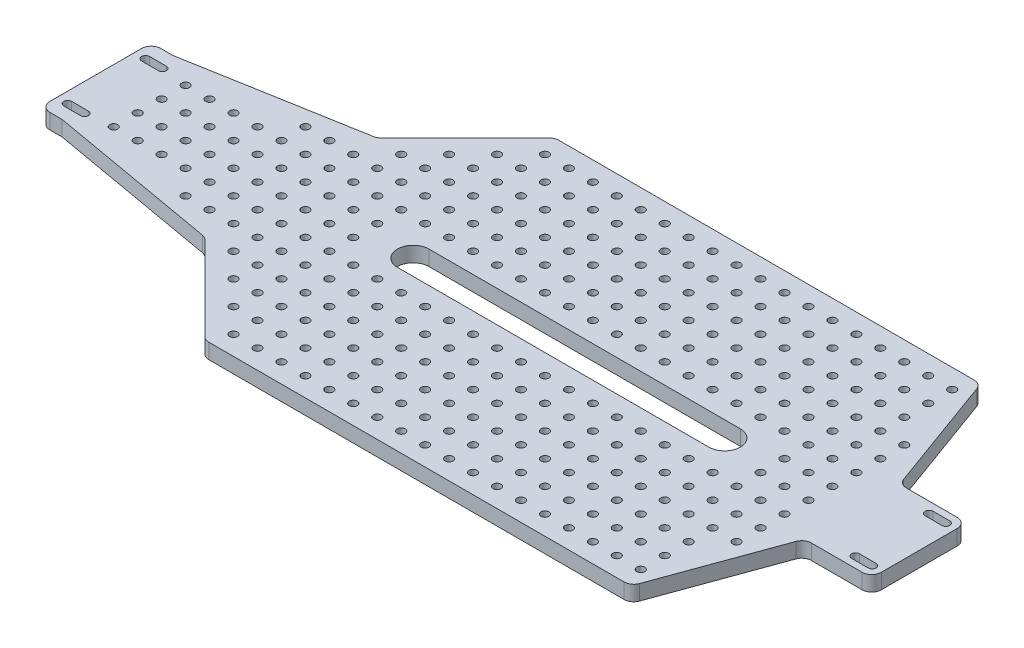
SolidWorks part; units mm, degrees
ref_plane "Front Plane" through (0, 0, 0) normal (0, 0, 1) x (1, 0, 0)
ref_plane "Top Plane" through (0, 0, 0) normal (0, 1, 0) x (1, 0, 0)
ref_plane "Right Plane" through (0, 0, 0) normal (1, 0, 0) x (0, 0, -1)
sketch "Sketch1" plane through (0, 0, 0) normal (0, 1, 0) x (1, 0, 0)
  line L0 (0, 32.5) -> (0, 0) construction
  line L17 (4.55, 39.385) -> (76.916, 52.1451)
  line L18 (0, 16.25) -> (325.2, 16.25) construction
  line L19 (-4.55, 39.385) -> (4.55, 39.385)
  line L20 (-4.55, 39.385) -> (-4.55, -6.885)
  line L21 (-4.55, -6.885) -> (4.55, -6.885)
  line L23 (-4.55, 39.385) -> (4.55, -6.885) construction
  line L24 (-4.55, -6.885) -> (4.55, 39.385) construction
  line L25 (311.2, -3.6) -> (339.2, -3.6)
  line L27 (311.2, 36.1) -> (339.2, 36.1)
  line L28 (339.2, -3.6) -> (339.2, 36.1)
  line L29 (311.2, -3.6) -> (339.2, 36.1) construction
  line L30 (311.2, 36.1) -> (339.2, -3.6) construction
  line L31 (202.9459, 16.25) -> (202.9459, 89.275) construction
  line L32 (291.8459, 89.275) -> (114.0459, 89.275)
  line L33 (311.2, 36.1) -> (291.8459, 89.275)
  line L34 (114.0459, 89.275) -> (76.916, 52.1451)
  line L35 (311.2, -3.6) -> (291.8459, -56.775)
  line L36 (291.8459, -56.775) -> (114.0459, -56.775)
  line L37 (114.0459, -56.775) -> (76.916, -19.6451)
  line L38 (4.55, -6.885) -> (76.916, -19.6451)
  line L39 (0, 32.5) -> (7, 32.5) construction
  line L40 (0, 34.15) -> (7, 34.15)
  line L41 (0, 30.85) -> (7, 30.85)
  line L42 (334.93, 31.625) -> (327.93, 31.625) construction
  line L43 (334.93, 29.975) -> (327.93, 29.975)
  line L44 (334.93, 33.275) -> (327.93, 33.275)
  line L45 (334.93, 0.875) -> (327.93, 0.875) construction
  line L46 (334.93, 2.525) -> (327.93, 2.525)
  line L47 (334.93, -0.775) -> (327.93, -0.775)
  line L48 (0, 0) -> (7, 0) construction
  line L49 (0, -1.65) -> (7, -1.65)
  line L50 (0, 1.65) -> (7, 1.65)
  circle A0 centre (0, 0) radius 1.65
  circle A1 centre (0, 32.5) radius 1.65 construction
  circle A4 centre (334.93, 31.625) radius 1.65 construction
  arc A5 (0, 34.15) -> (0, 30.85) centre (0, 32.5) ccw
  arc A6 (7, 30.85) -> (7, 34.15) centre (7, 32.5) ccw
  arc A7 (334.93, 29.975) -> (334.93, 33.275) centre (334.93, 31.625) ccw
  arc A8 (327.93, 33.275) -> (327.93, 29.975) centre (327.93, 31.625) ccw
  arc A9 (334.93, 2.525) -> (334.93, -0.775) centre (334.93, 0.875) cw
  arc A10 (327.93, -0.775) -> (327.93, 2.525) centre (327.93, 0.875) cw
  arc A11 (0, -1.65) -> (0, 1.65) centre (0, 0) cw
  arc A12 (7, 1.65) -> (7, -1.65) centre (7, 0) cw
  point P7 (3.5, 32.5)
  point P24 (202.9459, 89.275)
  point P32 (331.43, 31.625)
  point P40 (331.43, 0.875)
  point P46 (3.5, 0)
  dimension "D1" = 3.3
  dimension "D2" = 32.5
  dimension "D3" = 15.375
  dimension "D4" = 9.1
  dimension "D14" = 1.65
  dimension "D17" = 1.65
  dimension "D5" = 325.2
  dimension "D6" = 46.27
  dimension "D7" = 39.7
  dimension "D8" = 28
  dimension "D9" = 170
  dimension "D10" = 73.025
  dimension "D11" = 110
  dimension "D12" = 177.8
  dimension "D13" = 135
  dimension "D15" = 7
  dimension "D16" = 16.25
  dimension "D18" = 7
  dimension "D19" = 343.75
  dimension "D20" = 4.27
extrude "Boss-Extrude1" add sketch "Sketch1" along normal blind 6.35 contours L21 L38 L37 L36 L35 L25 L28 L27 L33 L32 L34 L17 L19 L20 A8 L44 A7 L43 A6 L41 A5 L40 L47 A10 L46 A9 L50 A12 L49 A0 region at (179.4962, 0, -16.25)
sketch "Sketch2" plane through (0, 6.35, 0) normal (0, 1, 0) x (1, 0, 0)
  line L1 (127.9459, 16.245) -> (257.9459, 16.245) construction
  line L4 (127.9459, 22.845) -> (257.9459, 22.845)
  line L5 (127.9459, 9.645) -> (257.9459, 9.645)
  circle A0 centre (117.9459, 81.245) radius 1.65
  circle A1 centre (127.9459, 81.245) radius 1.65
  circle A2 centre (137.9459, 81.245) radius 1.65
  circle A3 centre (147.9459, 81.245) radius 1.65
  circle A4 centre (157.9459, 81.245) radius 1.65
  circle A5 centre (167.9459, 81.245) radius 1.65
  circle A6 centre (177.9459, 81.245) radius 1.65
  circle A7 centre (187.9459, 81.245) radius 1.65
  circle A8 centre (197.9459, 81.245) radius 1.65
  circle A9 centre (207.9459, 81.245) radius 1.65
  circle A10 centre (217.9459, 81.245) radius 1.65
  circle A11 centre (227.9459, 81.245) radius 1.65
  circle A12 centre (237.9459, 81.245) radius 1.65
  circle A13 centre (247.9459, 81.245) radius 1.65
  circle A14 centre (257.9459, 81.245) radius 1.65
  circle A15 centre (267.9459, 81.245) radius 1.65
  circle A16 centre (277.9459, 81.245) radius 1.65
  circle A17 centre (287.9459, 81.245) radius 1.65
  circle A18 centre (127.9459, 71.245) radius 1.65
  circle A19 centre (137.9459, 71.245) radius 1.65
  circle A20 centre (147.9459, 71.245) radius 1.65
  circle A21 centre (157.9459, 71.245) radius 1.65
  circle A22 centre (167.9459, 71.245) radius 1.65
  circle A23 centre (177.9459, 71.245) radius 1.65
  circle A24 centre (187.9459, 71.245) radius 1.65
  circle A25 centre (197.9459, 71.245) radius 1.65
  circle A26 centre (207.9459, 71.245) radius 1.65
  circle A27 centre (217.9459, 71.245) radius 1.65
  circle A28 centre (227.9459, 71.245) radius 1.65
  circle A29 centre (237.9459, 71.245) radius 1.65
  circle A30 centre (247.9459, 71.245) radius 1.65
  circle A31 centre (257.9459, 71.245) radius 1.65
  circle A32 centre (267.9459, 71.245) radius 1.65
  circle A33 centre (277.9459, 71.245) radius 1.65
  circle A34 centre (287.9459, 71.245) radius 1.65
  circle A35 centre (127.9459, 61.245) radius 1.65
  circle A36 centre (137.9459, 61.245) radius 1.65
  circle A37 centre (147.9459, 61.245) radius 1.65
  circle A38 centre (157.9459, 61.245) radius 1.65
  circle A39 centre (167.9459, 61.245) radius 1.65
  circle A40 centre (177.9459, 61.245) radius 1.65
  circle A41 centre (187.9459, 61.245) radius 1.65
  circle A42 centre (197.9459, 61.245) radius 1.65
  circle A43 centre (207.9459, 61.245) radius 1.65
  circle A44 centre (217.9459, 61.245) radius 1.65
  circle A45 centre (227.9459, 61.245) radius 1.65
  circle A46 centre (237.9459, 61.245) radius 1.65
  circle A47 centre (247.9459, 61.245) radius 1.65
  circle A48 centre (257.9459, 61.245) radius 1.65
  circle A49 centre (267.9459, 61.245) radius 1.65
  circle A50 centre (277.9459, 61.245) radius 1.65
  circle A51 centre (287.9459, 61.245) radius 1.65
  circle A52 centre (127.9459, 51.245) radius 1.65
  circle A53 centre (137.9459, 51.245) radius 1.65
  circle A54 centre (147.9459, 51.245) radius 1.65
  circle A55 centre (157.9459, 51.245) radius 1.65
  circle A56 centre (167.9459, 51.245) radius 1.65
  circle A57 centre (177.9459, 51.245) radius 1.65
  circle A58 centre (187.9459, 51.245) radius 1.65
  circle A59 centre (197.9459, 51.245) radius 1.65
  circle A60 centre (207.9459, 51.245) radius 1.65
  circle A61 centre (217.9459, 51.245) radius 1.65
  circle A62 centre (227.9459, 51.245) radius 1.65
  circle A63 centre (237.9459, 51.245) radius 1.65
  circle A64 centre (247.9459, 51.245) radius 1.65
  circle A65 centre (257.9459, 51.245) radius 1.65
  circle A66 centre (267.9459, 51.245) radius 1.65
  circle A67 centre (277.9459, 51.245) radius 1.65
  circle A68 centre (287.9459, 51.245) radius 1.65
  circle A69 centre (127.9459, 41.245) radius 1.65
  circle A70 centre (137.9459, 41.245) radius 1.65
  circle A71 centre (147.9459, 41.245) radius 1.65
  circle A72 centre (157.9459, 41.245) radius 1.65
  circle A73 centre (167.9459, 41.245) radius 1.65
  circle A74 centre (177.9459, 41.245) radius 1.65
  circle A75 centre (187.9459, 41.245) radius 1.65
  circle A76 centre (197.9459, 41.245) radius 1.65
  circle A77 centre (207.9459, 41.245) radius 1.65
  circle A78 centre (217.9459, 41.245) radius 1.65
  circle A79 centre (227.9459, 41.245) radius 1.65
  circle A80 centre (237.9459, 41.245) radius 1.65
  circle A81 centre (247.9459, 41.245) radius 1.65
  circle A82 centre (257.9459, 41.245) radius 1.65
  circle A83 centre (267.9459, 41.245) radius 1.65
  circle A84 centre (277.9459, 41.245) radius 1.65
  circle A85 centre (287.9459, 41.245) radius 1.65
  circle A86 centre (127.9459, 31.245) radius 1.65
  circle A87 centre (137.9459, 31.245) radius 1.65
  circle A88 centre (147.9459, 31.245) radius 1.65
  circle A89 centre (157.9459, 31.245) radius 1.65
  circle A90 centre (167.9459, 31.245) radius 1.65
  circle A91 centre (177.9459, 31.245) radius 1.65
  circle A92 centre (187.9459, 31.245) radius 1.65
  circle A93 centre (197.9459, 31.245) radius 1.65
  circle A94 centre (207.9459, 31.245) radius 1.65
  circle A95 centre (217.9459, 31.245) radius 1.65
  circle A96 centre (227.9459, 31.245) radius 1.65
  circle A97 centre (237.9459, 31.245) radius 1.65
  circle A98 centre (247.9459, 31.245) radius 1.65
  circle A99 centre (257.9459, 31.245) radius 1.65
  circle A100 centre (267.9459, 31.245) radius 1.65
  circle A101 centre (277.9459, 31.245) radius 1.65
  circle A102 centre (287.9459, 31.245) radius 1.65
  circle A118 centre (277.9459, 21.245) radius 1.65
  circle A119 centre (287.9459, 21.245) radius 1.65
  circle A135 centre (277.9459, 11.245) radius 1.65
  circle A136 centre (287.9459, 11.245) radius 1.65
  circle A137 centre (127.9459, 1.245) radius 1.65
  circle A138 centre (137.9459, 1.245) radius 1.65
  circle A139 centre (147.9459, 1.245) radius 1.65
  circle A140 centre (157.9459, 1.245) radius 1.65
  circle A141 centre (167.9459, 1.245) radius 1.65
  circle A142 centre (177.9459, 1.245) radius 1.65
  circle A143 centre (187.9459, 1.245) radius 1.65
  circle A144 centre (197.9459, 1.245) radius 1.65
  circle A145 centre (207.9459, 1.245) radius 1.65
  circle A146 centre (217.9459, 1.245) radius 1.65
  circle A147 centre (227.9459, 1.245) radius 1.65
  circle A148 centre (237.9459, 1.245) radius 1.65
  circle A149 centre (247.9459, 1.245) radius 1.65
  circle A150 centre (257.9459, 1.245) radius 1.65
  circle A151 centre (267.9459, 1.245) radius 1.65
  circle A152 centre (277.9459, 1.245) radius 1.65
  circle A153 centre (287.9459, 1.245) radius 1.65
  circle A154 centre (127.9459, -8.755) radius 1.65
  circle A155 centre (137.9459, -8.755) radius 1.65
  circle A156 centre (147.9459, -8.755) radius 1.65
  circle A157 centre (157.9459, -8.755) radius 1.65
  circle A158 centre (167.9459, -8.755) radius 1.65
  circle A159 centre (177.9459, -8.755) radius 1.65
  circle A160 centre (187.9459, -8.755) radius 1.65
  circle A161 centre (197.9459, -8.755) radius 1.65
  circle A162 centre (207.9459, -8.755) radius 1.65
  circle A163 centre (217.9459, -8.755) radius 1.65
  circle A164 centre (227.9459, -8.755) radius 1.65
  circle A165 centre (237.9459, -8.755) radius 1.65
  circle A166 centre (247.9459, -8.755) radius 1.65
  circle A167 centre (257.9459, -8.755) radius 1.65
  circle A168 centre (267.9459, -8.755) radius 1.65
  circle A169 centre (277.9459, -8.755) radius 1.65
  circle A170 centre (287.9459, -8.755) radius 1.65
  circle A171 centre (127.9459, -18.755) radius 1.65
  circle A172 centre (137.9459, -18.755) radius 1.65
  circle A173 centre (147.9459, -18.755) radius 1.65
  circle A174 centre (157.9459, -18.755) radius 1.65
  circle A175 centre (167.9459, -18.755) radius 1.65
  circle A176 centre (177.9459, -18.755) radius 1.65
  circle A177 centre (187.9459, -18.755) radius 1.65
  circle A178 centre (197.9459, -18.755) radius 1.65
  circle A179 centre (207.9459, -18.755) radius 1.65
  circle A180 centre (217.9459, -18.755) radius 1.65
  circle A181 centre (227.9459, -18.755) radius 1.65
  circle A182 centre (237.9459, -18.755) radius 1.65
  circle A183 centre (247.9459, -18.755) radius 1.65
  circle A184 centre (257.9459, -18.755) radius 1.65
  circle A185 centre (267.9459, -18.755) radius 1.65
  circle A186 centre (277.9459, -18.755) radius 1.65
  circle A187 centre (287.9459, -18.755) radius 1.65
  circle A188 centre (127.9459, -28.755) radius 1.65
  circle A189 centre (137.9459, -28.755) radius 1.65
  circle A190 centre (147.9459, -28.755) radius 1.65
  circle A191 centre (157.9459, -28.755) radius 1.65
  circle A192 centre (167.9459, -28.755) radius 1.65
  circle A193 centre (177.9459, -28.755) radius 1.65
  circle A194 centre (187.9459, -28.755) radius 1.65
  circle A195 centre (197.9459, -28.755) radius 1.65
  circle A196 centre (207.9459, -28.755) radius 1.65
  circle A197 centre (217.9459, -28.755) radius 1.65
  circle A198 centre (227.9459, -28.755) radius 1.65
  circle A199 centre (237.9459, -28.755) radius 1.65
  circle A200 centre (247.9459, -28.755) radius 1.65
  circle A201 centre (257.9459, -28.755) radius 1.65
  circle A202 centre (267.9459, -28.755) radius 1.65
  circle A203 centre (277.9459, -28.755) radius 1.65
  circle A204 centre (287.9459, -28.755) radius 1.65
  circle A205 centre (127.9459, -38.755) radius 1.65
  circle A206 centre (137.9459, -38.755) radius 1.65
  circle A207 centre (147.9459, -38.755) radius 1.65
  circle A208 centre (157.9459, -38.755) radius 1.65
  circle A209 centre (167.9459, -38.755) radius 1.65
  circle A210 centre (177.9459, -38.755) radius 1.65
  circle A211 centre (187.9459, -38.755) radius 1.65
  circle A212 centre (197.9459, -38.755) radius 1.65
  circle A213 centre (207.9459, -38.755) radius 1.65
  circle A214 centre (217.9459, -38.755) radius 1.65
  circle A215 centre (227.9459, -38.755) radius 1.65
  circle A216 centre (237.9459, -38.755) radius 1.65
  circle A217 centre (247.9459, -38.755) radius 1.65
  circle A218 centre (257.9459, -38.755) radius 1.65
  circle A219 centre (267.9459, -38.755) radius 1.65
  circle A220 centre (277.9459, -38.755) radius 1.65
  circle A221 centre (287.9459, -38.755) radius 1.65
  circle A222 centre (127.9459, -48.755) radius 1.65
  circle A223 centre (137.9459, -48.755) radius 1.65
  circle A224 centre (147.9459, -48.755) radius 1.65
  circle A225 centre (157.9459, -48.755) radius 1.65
  circle A226 centre (167.9459, -48.755) radius 1.65
  circle A227 centre (177.9459, -48.755) radius 1.65
  circle A228 centre (187.9459, -48.755) radius 1.65
  circle A229 centre (197.9459, -48.755) radius 1.65
  circle A230 centre (207.9459, -48.755) radius 1.65
  circle A231 centre (217.9459, -48.755) radius 1.65
  circle A232 centre (227.9459, -48.755) radius 1.65
  circle A233 centre (237.9459, -48.755) radius 1.65
  circle A234 centre (247.9459, -48.755) radius 1.65
  circle A235 centre (257.9459, -48.755) radius 1.65
  circle A236 centre (267.9459, -48.755) radius 1.65
  circle A237 centre (277.9459, -48.755) radius 1.65
  circle A238 centre (287.9459, -48.755) radius 1.65
  circle A239 centre (117.9459, 71.245) radius 1.65
  circle A240 centre (117.9459, 61.245) radius 1.65
  circle A241 centre (117.9459, 51.245) radius 1.65
  circle A242 centre (117.9459, 41.245) radius 1.65
  circle A243 centre (117.9459, 31.245) radius 1.65
  circle A246 centre (117.9459, 1.245) radius 1.65
  circle A247 centre (117.9459, -8.755) radius 1.65
  circle A248 centre (117.9459, -18.755) radius 1.65
  circle A249 centre (117.9459, -28.755) radius 1.65
  circle A250 centre (117.9459, -38.755) radius 1.65
  circle A251 centre (117.9459, -48.755) radius 1.65
  arc A262 (127.9459, 22.845) -> (127.9459, 9.645) centre (127.9459, 16.245) ccw
  arc A263 (257.9459, 9.645) -> (257.9459, 22.845) centre (257.9459, 16.245) ccw
  circle A264 centre (297.9459, 51.245) radius 1.65
  circle A265 centre (297.9459, 41.245) radius 1.65
  circle A266 centre (297.9459, 31.245) radius 1.65
  circle A268 centre (297.9459, 21.245) radius 1.65
  circle A269 centre (297.9459, 11.245) radius 1.65
  circle A270 centre (297.9459, 1.245) radius 1.65
  circle A271 centre (297.9459, -8.755) radius 1.65
  circle A272 centre (297.9459, -18.755) radius 1.65
  circle A276 centre (107.9459, 71.245) radius 1.65
  circle A277 centre (97.9459, 71.245) radius 1.65 [skipped]
  circle A278 centre (87.9459, 71.245) radius 1.65 [skipped]
  circle A279 centre (97.9459, 61.245) radius 1.65
  circle A280 centre (87.9459, 61.245) radius 1.65 [skipped]
  circle A281 centre (97.9459, 51.245) radius 1.65
  circle A282 centre (87.9459, 51.245) radius 1.65
  circle A283 centre (97.9459, 41.245) radius 1.65
  circle A284 centre (87.9459, 41.245) radius 1.65
  circle A285 centre (97.9459, 31.245) radius 1.65
  circle A286 centre (87.9459, 31.245) radius 1.65
  circle A287 centre (97.9459, 21.245) radius 1.65
  circle A288 centre (87.9459, 21.245) radius 1.65
  circle A289 centre (97.9459, 11.245) radius 1.65
  circle A290 centre (87.9459, 11.245) radius 1.65
  circle A291 centre (97.9459, 1.245) radius 1.65
  circle A292 centre (87.9459, 1.245) radius 1.65
  circle A293 centre (97.9459, -8.755) radius 1.65
  circle A294 centre (87.9459, -8.755) radius 1.65
  circle A295 centre (97.9459, -18.755) radius 1.65
  circle A296 centre (87.9459, -18.755) radius 1.65
  circle A297 centre (97.9459, -28.755) radius 1.65
  circle A298 centre (87.9459, -28.755) radius 1.65 [skipped]
  circle A299 centre (97.9459, -38.755) radius 1.65 [skipped]
  circle A300 centre (87.9459, -38.755) radius 1.65 [skipped]
  circle A301 centre (107.9459, 61.245) radius 1.65
  circle A302 centre (107.9459, 51.245) radius 1.65
  circle A303 centre (107.9459, 41.245) radius 1.65
  circle A304 centre (107.9459, 31.245) radius 1.65
  circle A305 centre (107.9459, 21.245) radius 1.65
  circle A306 centre (107.9459, 11.245) radius 1.65
  circle A307 centre (107.9459, 1.245) radius 1.65
  circle A308 centre (107.9459, -8.755) radius 1.65
  circle A309 centre (107.9459, -18.755) radius 1.65
  circle A310 centre (107.9459, -28.755) radius 1.65
  circle A311 centre (107.9459, -38.755) radius 1.65
  circle A312 centre (77.9459, 41.245) radius 1.65
  circle A313 centre (67.9459, 41.245) radius 1.65
  circle A314 centre (57.9459, 41.245) radius 1.65
  circle A320 centre (67.9459, 31.245) radius 1.65
  circle A321 centre (57.9459, 31.245) radius 1.65
  circle A322 centre (47.9459, 31.245) radius 1.65
  circle A323 centre (37.9459, 31.245) radius 1.65
  circle A324 centre (27.9459, 31.245) radius 1.65
  circle A325 centre (17.9459, 31.245) radius 1.65
  circle A327 centre (67.9459, 21.245) radius 1.65
  circle A328 centre (57.9459, 21.245) radius 1.65
  circle A329 centre (47.9459, 21.245) radius 1.65
  circle A330 centre (37.9459, 21.245) radius 1.65
  circle A331 centre (27.9459, 21.245) radius 1.65
  circle A332 centre (17.9459, 21.245) radius 1.65
  circle A334 centre (67.9459, 11.245) radius 1.65
  circle A335 centre (57.9459, 11.245) radius 1.65
  circle A336 centre (47.9459, 11.245) radius 1.65
  circle A337 centre (37.9459, 11.245) radius 1.65
  circle A338 centre (27.9459, 11.245) radius 1.65
  circle A339 centre (17.9459, 11.245) radius 1.65
  circle A341 centre (67.9459, 1.245) radius 1.65
  circle A342 centre (57.9459, 1.245) radius 1.65
  circle A343 centre (47.9459, 1.245) radius 1.65
  circle A344 centre (37.9459, 1.245) radius 1.65
  circle A345 centre (27.9459, 1.245) radius 1.65
  circle A346 centre (17.9459, 1.245) radius 1.65
  circle A348 centre (67.9459, -8.755) radius 1.65
  circle A349 centre (57.9459, -8.755) radius 1.65
  circle A355 centre (77.9459, 31.245) radius 1.65
  circle A356 centre (77.9459, 21.245) radius 1.65
  circle A357 centre (77.9459, 11.245) radius 1.65
  circle A358 centre (77.9459, 1.245) radius 1.65
  circle A359 centre (77.9459, -8.755) radius 1.65
  circle A361 centre (27.9459, 41.245) radius 1.65 [skipped]
  circle A362 centre (17.9459, 41.245) radius 1.65 [skipped]
  circle A364 centre (27.9459, -8.755) radius 1.65 [skipped]
  circle A365 centre (17.9459, -8.755) radius 1.65 [skipped]
  circle A366 centre (37.9459, 41.245) radius 1.65 [skipped]
  circle A367 centre (37.9459, -8.755) radius 1.65 [skipped]
  circle A368 centre (47.9459, 41.245) radius 1.65 [skipped]
  circle A369 centre (47.9459, -8.755) radius 1.65 [skipped]
  circle A370 centre (127.9459, 21.245) radius 1.65 [skipped]
  circle A371 centre (137.9459, 21.245) radius 1.65 [skipped]
  circle A372 centre (147.9459, 21.245) radius 1.65 [skipped]
  circle A373 centre (157.9459, 21.245) radius 1.65 [skipped]
  circle A374 centre (167.9459, 21.245) radius 1.65 [skipped]
  circle A375 centre (177.9459, 21.245) radius 1.65 [skipped]
  circle A376 centre (187.9459, 21.245) radius 1.65 [skipped]
  circle A377 centre (197.9459, 21.245) radius 1.65 [skipped]
  circle A378 centre (207.9459, 21.245) radius 1.65 [skipped]
  circle A379 centre (217.9459, 21.245) radius 1.65 [skipped]
  circle A380 centre (227.9459, 21.245) radius 1.65 [skipped]
  circle A381 centre (237.9459, 21.245) radius 1.65 [skipped]
  circle A382 centre (247.9459, 21.245) radius 1.65 [skipped]
  circle A383 centre (257.9459, 21.245) radius 1.65 [skipped]
  circle A384 centre (267.9459, 21.245) radius 1.65 [skipped]
  circle A385 centre (127.9459, 11.245) radius 1.65 [skipped]
  circle A386 centre (137.9459, 11.245) radius 1.65 [skipped]
  circle A387 centre (147.9459, 11.245) radius 1.65 [skipped]
  circle A388 centre (157.9459, 11.245) radius 1.65 [skipped]
  circle A389 centre (167.9459, 11.245) radius 1.65 [skipped]
  circle A390 centre (177.9459, 11.245) radius 1.65 [skipped]
  circle A391 centre (187.9459, 11.245) radius 1.65 [skipped]
  circle A392 centre (197.9459, 11.245) radius 1.65 [skipped]
  circle A393 centre (207.9459, 11.245) radius 1.65 [skipped]
  circle A394 centre (217.9459, 11.245) radius 1.65 [skipped]
  circle A395 centre (227.9459, 11.245) radius 1.65 [skipped]
  circle A396 centre (237.9459, 11.245) radius 1.65 [skipped]
  circle A397 centre (247.9459, 11.245) radius 1.65 [skipped]
  circle A398 centre (257.9459, 11.245) radius 1.65 [skipped]
  circle A399 centre (267.9459, 11.245) radius 1.65 [skipped]
  circle A400 centre (117.9459, 21.245) radius 1.65 [skipped]
  circle A401 centre (117.9459, 11.245) radius 1.65 [skipped]
  point P210 (192.9459, 16.245)
  dimension "D1" = 3.3
  dimension "D5" = 6.6
  dimension "D8" = 10
  dimension "D11" = 10
  dimension "D6" = 10
  dimension "D2" = 3
  dimension "D9" = 3.9
  dimension "D14" = 8.03
  dimension "D3" = 18
  dimension "D4" = 14
  dimension "D10" = 12
  dimension "D12" = 7
  dimension "D13" = 6
  dimension "D7" = 8
extrude "Cut-Extrude1" cut sketch "Sketch2" against normal through all
fillet "Fillet1" radius 4 12 edges at (76.916, 3.175, -52.1451) (114.0459, 3.175, -89.275) (291.8459, 3.175, -89.275) (311.2, 3.175, -36.1) (339.2, 3.175, -36.1) (339.2, 3.175, 3.6) (311.2, 3.175, 3.6) (291.8459, 3.175, 56.775) (-4.55, 3.175, -39.385) (-4.55, 3.175, 6.885) (76.916, 3.175, 19.6451) (114.0459, 3.175, 56.775)
